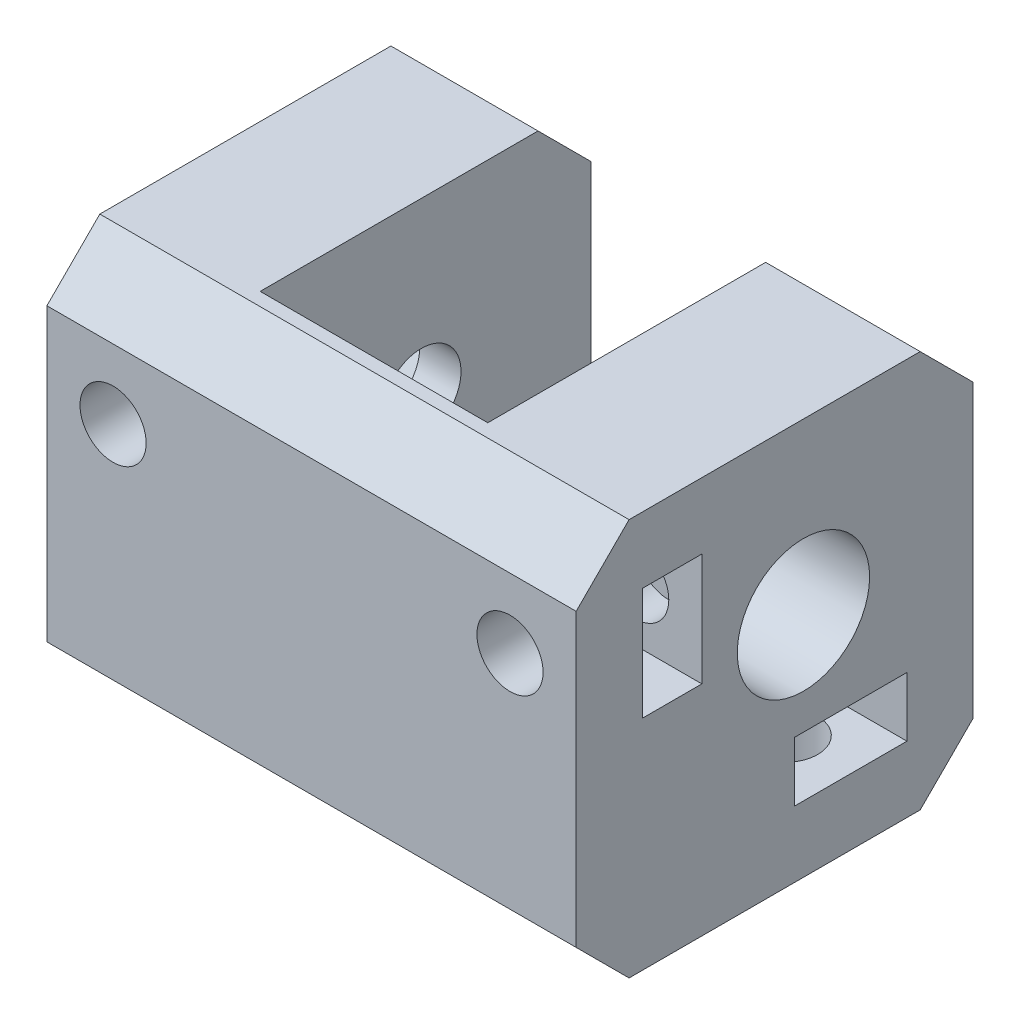
SolidWorks part; units mm, degrees
ref_plane "Front Plane" through (0, 0, 0) normal (0, 0, 1) x (1, 0, 0)
ref_plane "Top Plane" through (0, 0, 0) normal (0, 1, 0) x (1, 0, 0)
ref_plane "Right Plane" through (0, 0, 0) normal (1, 0, 0) x (0, 0, -1)
sketch "Sketch1" plane through (0, 0, 0) normal (0, 0, 1) x (1, 0, 0)
  line L0 (-71.5929, 28.752) -> (-71.5929, 34.452) construction
  line L1 (-31.5929, 27.752) -> (-71.5929, 27.752)
  line L2 (-31.5929, 27.752) -> (-31.5929, 57.752)
  line L3 (-31.5929, 57.752) -> (-71.5929, 57.752)
  line L4 (-71.5929, 27.752) -> (-71.5929, 57.752)
  line L5 (-64.8929, 27.752) -> (-70.5929, 27.752) construction
  line L6 (-31.5929, 34.452) -> (-31.5929, 28.752) construction
  dimension "D1" = 30
extrude "Boss-Extrude1" add sketch "Sketch1" along normal blind 30 contours L3 L4 L1 L2
sketch "Sketch2" plane through (0, 57.752, 0) normal (0, 1, 0) x (1, 0, 0)
  line L0 (-31.5929, 0) -> (-71.5929, 0) construction
  line L1 (-43.2729, -25) -> (-60.4729, -25)
  line L2 (-43.2729, -25) -> (-43.2729, 8.7289)
  line L3 (-43.2729, 8.7289) -> (-60.4729, 8.7289)
  line L4 (-60.4729, -25) -> (-60.4729, 8.7289)
  line L6 (-45.5729, -15.5089) -> (-45.5729, -10.5089) construction
  line L8 (-58.1729, -6.0089) -> (-58.1729, -20.0089) construction
  dimension "D1" = 25
  dimension "D2" = 2.3
  dimension "D3" = 2.3
extrude "Cut-Extrude1" cut sketch "Sketch2" against normal offset from surface (25 mm away) 5 up to face at (-51.5929, 27.752, 15)
sketch "Sketch3" plane through (-31.5929, 0, 0) normal (1, 0, 0) x (0, 0, -1)
  line L0 (0, 57.752) -> (-30, 27.752) construction
  line L1 (-30, 57.752) -> (0, 57.752) construction
  line L2 (0, 27.752) -> (0, 57.752) construction
  circle A1 centre (-12.8221, 44.9299) radius 2.5 construction
  circle A2 centre (-12.8221, 44.9299) radius 3
  dimension "D1" = 6
extrude "Cut-Extrude2" cut sketch "Sketch3" against normal through all contours A2
sketch "Sketch4" plane through (-31.5929, 0, 0) normal (1, 0, 0) x (0, 0, -1)
  line L0 (0, 57.752) -> (-30, 27.752) construction
  line L1 (-5, 32.752) -> (-13.5, 32.752)
  line L2 (-5, 32.752) -> (-5, 37.252)
  line L3 (-5, 37.252) -> (-13.5, 37.252)
  line L4 (-13.5, 32.752) -> (-13.5, 37.252)
  line L5 (-25, 52.752) -> (-25, 44.252)
  line L6 (-25, 52.752) -> (-20.5, 52.752)
  line L7 (-20.5, 52.752) -> (-20.5, 44.252)
  line L8 (-25, 44.252) -> (-20.5, 44.252)
  line L9 (0, 27.752) -> (0, 57.752) construction
  line L10 (-30, 27.752) -> (0, 27.752) construction
  dimension "D1" = 8.5
  dimension "D2" = 4.5
  dimension "D3" = 5
  dimension "D4" = 5
extrude "Cut-Extrude3" cut sketch "Sketch4" against normal blind 9
extrude "Cut-Extrude4" cut sketch "Sketch4<2>" along normal blind 9 from surface starting at face at (-71.5929, 44.9299, 9.8221)
sketch "Sketch4<2>" plane through (-31.5929, 0, 0) normal (1, 0, 0) x (0, 0, -1) same geometry as "Sketch4"
sketch "Sketch5" plane through (0, 0, 30) normal (0, 0, 1) x (1, 0, 0)
  line L0 (-62.5929, 44.252) -> (-62.5929, 52.752) construction
  line L1 (-40.5929, 52.752) -> (-40.5929, 44.252) construction
  line L2 (-62.5929, 44.252) -> (-62.5929, 52.752) construction
  line L3 (-40.5929, 52.752) -> (-40.5929, 44.252) construction
  line L4 (-66.5929, 48.502) -> (-36.5929, 48.502) construction
  circle A0 centre (-66.5929, 48.502) radius 2.5
  circle A1 centre (-36.5929, 48.502) radius 2.5
  point P8 (-62.5929, 48.502)
  dimension "D3" = 5
  dimension "D1" = 4
  dimension "D2" = 4
extrude "Cut-Extrude5" cut sketch "Sketch5" against normal blind 12
ref_plane "Plane1" through (0, 28.876, 28.876) normal (0, -0.7071, -0.7071) x (-1, 0, 0)
mirror "Mirror1" about plane through (0, 28.876, 28.876) normal (0, -0.7071, -0.7071) of "Cut-Extrude5"
chamfer "Chamfer1" distance 4 angle 45 5 edges at (-51.5929, 57.752, 30) (-66.0329, 57.752, 0) (-37.4329, 57.752, 0) (-51.5929, 27.752, 0) (-51.5929, 27.752, 30)
sketch "Sketch6" plane through (-31.5929, 0, 0) normal (1, 0, 0) x (0, 0, -1)
  circle A0 centre (-12.8221, 44.9299) radius 5
  dimension "D1" = 10
extrude "Cut-Extrude6" cut sketch "Sketch6" against normal blind 8
sketch "Sketch7" plane through (-71.5929, 0, 0) normal (-1, 0, 0) x (0, 0, 1)
  line L0 (26, 57.752) -> (4, 57.752) construction
  line L1 (15.3047, 40.6299) -> (17.7873, 44.9299)
  line L2 (17.7873, 44.9299) -> (15.3047, 49.2299)
  line L3 (15.3047, 49.2299) -> (10.3395, 49.2299)
  line L4 (10.3395, 49.2299) -> (7.8569, 44.9299)
  line L5 (7.8569, 44.9299) -> (10.3395, 40.6299)
  line L6 (10.3395, 40.6299) -> (15.3047, 40.6299)
  circle A0 centre (12.8221, 44.9299) radius 4.3 construction
  dimension "D1" = 8.6
extrude "Cut-Extrude7" cut sketch "Sketch7" against normal blind 8
